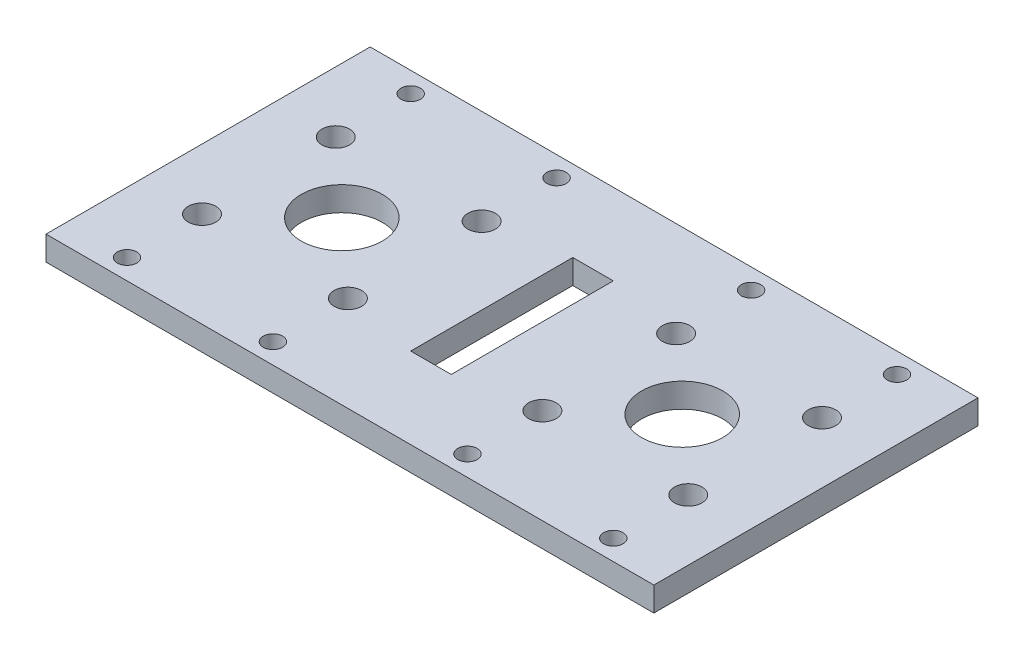
SolidWorks part; units mm, degrees
ref_plane "Front Plane" through (0, 0, 0) normal (0, 0, 1) x (1, 0, 0)
ref_plane "Top Plane" through (0, 0, 0) normal (0, 1, 0) x (1, 0, 0)
ref_plane "Right Plane" through (0, 0, 0) normal (1, 0, 0) x (0, 0, -1)
sketch "Sketch1" plane through (0, 0, 0) normal (0, 1, 0) x (1, 0, 0)
  line L0 (0, 0) -> (0, -14.43) construction
  line L1 (-37.5, 20) -> (37.5, 20)
  line L2 (-37.5, 20) -> (-37.5, -20)
  line L3 (-37.5, -20) -> (37.5, -20)
  line L4 (37.5, 20) -> (37.5, -20)
  line L5 (-37.5, 20) -> (37.5, -20) construction
  line L6 (-37.5, -20) -> (37.5, 20) construction
  line L7 (0, 0) -> (6.508, 0) construction
  line L8 (-2.5, 10) -> (2.5, 10)
  line L9 (-2.5, 10) -> (-2.5, -10)
  line L10 (-2.5, -10) -> (2.5, -10)
  line L11 (2.5, 10) -> (2.5, -10)
  line L12 (-2.5, 10) -> (2.5, -10) construction
  line L13 (-2.5, -10) -> (2.5, 10) construction
  circle A0 centre (-21, 0) radius 5
  circle A1 centre (-30, 8.25) radius 1.7
  circle A2 centre (-12, 8.25) radius 1.7
  circle A3 centre (-12, -8.25) radius 1.7
  circle A4 centre (-30, -8.25) radius 1.7
  circle A5 centre (12, 8.25) radius 1.7
  circle A6 centre (12, -8.25) radius 1.7
  circle A7 centre (21, 0) radius 5
  circle A8 centre (30, -8.25) radius 1.7
  circle A9 centre (30, 8.25) radius 1.7
  circle A10 centre (-30, -17.5) radius 1.1976
  circle A11 centre (-12, -17.5) radius 1.1976
  circle A12 centre (12, -17.5) radius 1.1976
  circle A13 centre (30, -17.5) radius 1.1976
  circle A14 centre (30, 17.5) radius 1.1976
  circle A15 centre (12, 17.5) radius 1.1976
  circle A16 centre (-12, 17.5) radius 1.1976
  circle A17 centre (-30, 17.5) radius 1.1976
  point P0 (0, 0)
  dimension "D3" = 10
  dimension "D4" = 21
  dimension "D5" = 8.25
  dimension "D6" = 9
  dimension "D9" = 5
  dimension "D11" = 20
  dimension "D12" = 7.5
  dimension "D13" = 25.5
  dimension "D14" = 7.5
  dimension "D15" = 2.5
  dimension "D1" = 75
  dimension "D2" = 40
  dimension "D10" = 20
  dimension "D7" = 2
  dimension "D8" = 2
  dimension "D16" = 2
extrude "Boss-Extrude1" add sketch "Sketch1" along normal blind 3
